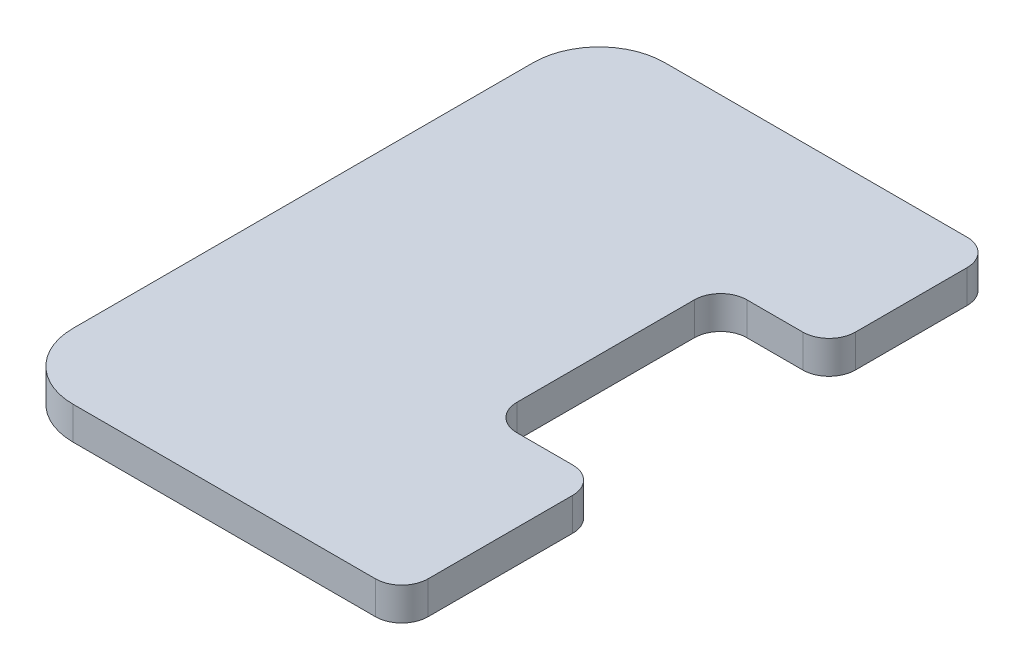
SolidWorks part; units mm, degrees
ref_plane "Front Plane" through (0, 0, 0) normal (0, 0, 1) x (1, 0, 0)
ref_plane "Top Plane" through (0, 0, 0) normal (0, 1, 0) x (1, 0, 0)
ref_plane "Right Plane" through (0, 0, 0) normal (1, 0, 0) x (0, 0, -1)
sketch "Sketch1" plane through (0, 0, 0) normal (0, 1, 0) x (1, 0, 0)
  line L1 (-19.05, -28.575) -> (19.05, -28.575)
  line L2 (-19.05, -28.575) -> (-19.05, 28.575)
  line L3 (-19.05, 28.575) -> (19.05, 28.575)
  line L4 (19.05, -28.575) -> (19.05, 28.575)
  line L5 (-19.05, -28.575) -> (19.05, 28.575) construction
  line L6 (-19.05, 28.575) -> (19.05, -28.575) construction
  point P0 (0, 0)
  dimension "D1" = 57.15
  dimension "D2" = 38.1
extrude "Boss-Extrude1" add sketch "Sketch1" along normal blind 3.175
sketch "Sketch2" plane through (0, 3.175, 0) normal (0, 1, 0) x (1, 0, 0)
  line L0 (19.05, -9.525) -> (8.5725, -9.525)
  line L1 (19.05, -28.575) -> (19.05, 28.575) construction
  line L2 (8.5725, -9.525) -> (8.5725, 12.7)
  line L3 (8.5725, 12.7) -> (19.05, 12.7)
  line L4 (19.05, 28.575) -> (-19.05, 28.575) construction
  line L5 (-19.05, -28.575) -> (19.05, -28.575) construction
  line L6 (19.05, -9.525) -> (19.05, 12.7)
  dimension "D1" = 15.875
  dimension "D2" = 19.05
  dimension "D3" = 10.4775
extrude "Cut-Extrude2" cut sketch "Sketch2" against normal through all
fillet "Fillet1" radius 2.54 6 edges at (19.05, 1.5875, 28.575) (19.05, 1.5875, -28.575) (19.05, 1.5875, 9.525) (8.5725, 1.5875, 9.525) (19.05, 1.5875, -12.7) (8.5725, 1.5875, -12.7)
fillet "Fillet2" radius 6.35 2 edges at (-19.05, 1.5875, 28.575) (-19.05, 1.5875, -28.575)
